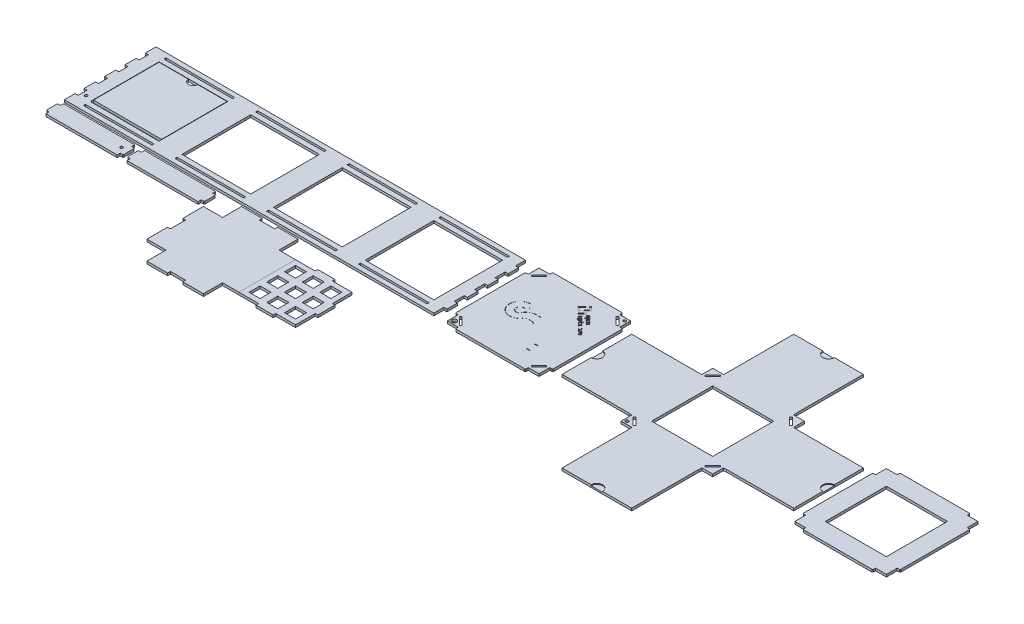
SolidWorks part; units mm, degrees
ref_plane "Front" through (0, 0, 0) normal (0, 0, 1) x (1, 0, 0)
ref_plane "Top" through (0, 0, 0) normal (0, 1, 0) x (1, 0, 0)
ref_plane "Right" through (0, 0, 0) normal (1, 0, 0) x (0, 0, -1)
sketch "Sketch1" plane through (0, 0, 0) normal (0, 1, 0) x (1, 0, 0)
  line L0 (0, 0) -> (228.6, 0) construction
  line L2 (-76.2, 76.2) -> (-76.2, -76.2) construction
  line L4 (76.2, 76.2) -> (76.2, -76.2) construction
  line L5 (-76.2, 76.2) -> (76.2, -76.2) construction
  line L6 (-76.2, -76.2) -> (76.2, 76.2) construction
  line L11 (76.2, 76.2) -> (228.6, 76.2)
  line L12 (76.2, 76.2) -> (76.2, -76.2) construction
  line L13 (76.2, -76.2) -> (228.6, -76.2)
  line L14 (228.6, 76.2) -> (228.6, -76.2) construction
  line L19 (-76.2, -76.2) -> (-228.6, -76.2)
  line L20 (-76.2, -76.2) -> (-76.2, 76.2) construction
  line L21 (-76.2, 76.2) -> (-228.6, 76.2)
  line L28 (76.2, -76.2) -> (-76.2, -76.2)
  line L34 (76.2, 76.2) -> (-76.2, 76.2)
  line L35 (-228.6, 76.2) -> (-228.6, -76.2) construction
  line L43 (-228.6, 76.2) -> (-381, 76.2)
  line L44 (-381, 76.2) -> (-381, -76.2) construction
  line L45 (-381, -76.2) -> (-228.6, -76.2)
  line L46 (228.6, 76.2) -> (228.6, 59.6392)
  line L47 (228.6, 59.6392) -> (233.68, 59.6392)
  line L48 (233.68, 59.6392) -> (233.68, 42.2402)
  line L49 (233.68, 42.2402) -> (228.6, 42.2402)
  line L50 (228.6, 42.2402) -> (228.6, 25.6794)
  line L51 (228.6, 25.6794) -> (233.68, 25.6794)
  line L63 (233.68, 25.6794) -> (233.68, 8.2804)
  line L64 (233.68, 8.2804) -> (228.6, 8.2804)
  line L65 (228.6, 8.2804) -> (228.6, -8.2804)
  line L66 (228.6, -8.2804) -> (233.68, -8.2804)
  line L67 (233.68, -8.2804) -> (233.68, -25.6794)
  line L68 (233.68, -25.6794) -> (228.6, -25.6794)
  line L69 (228.6, -25.6794) -> (228.6, -42.2402)
  line L70 (228.6, -42.2402) -> (233.68, -42.2402)
  line L71 (233.68, -42.2402) -> (233.68, -59.6392)
  line L72 (233.68, -59.6392) -> (228.6, -59.6392)
  line L73 (228.6, -59.6392) -> (228.6, -76.2)
  line L74 (-381, 76.2) -> (-386.08, 76.2)
  line L76 (-386.08, 58.5597) -> (-381, 58.5597)
  line L78 (-381, 43.3197) -> (-386.08, 43.3197)
  line L80 (-386.08, 24.5999) -> (-381, 24.5999)
  line L82 (-381, 9.3599) -> (-386.08, 9.3599)
  line L84 (-386.08, -9.3599) -> (-381, -9.3599)
  line L86 (-381, -24.5999) -> (-386.08, -24.5999)
  line L88 (-386.08, -43.3197) -> (-381, -43.3197)
  line L90 (-381, -58.5597) -> (-386.08, -58.5597)
  line L92 (-386.08, -76.2) -> (-381, -76.2)
  line L93 (233.68, 16.9799) -> (-381, 16.9799) construction
  line L94 (-381, 50.9397) -> (233.68, 50.9397) construction
  line L95 (-386.08, 76.2) -> (-386.08, 58.5597)
  line L96 (-386.08, 43.3197) -> (-386.08, 24.5999)
  line L97 (-381, 58.5597) -> (-381, 43.3197)
  line L98 (-381, 24.5999) -> (-381, 9.3599)
  line L99 (-381, -9.3599) -> (-381, -24.5999)
  line L100 (-381, -43.3197) -> (-381, -58.5597)
  line L101 (-381, -50.9397) -> (233.68, -50.9397) construction
  line L102 (-381, -16.9799) -> (233.68, -16.9799) construction
  line L103 (-386.08, 9.3599) -> (-386.08, -9.3599)
  line L104 (-386.08, -24.5999) -> (-386.08, -43.3197)
  line L105 (-386.08, -58.5597) -> (-386.08, -76.2)
  point P0 (0, 0)
  dimension "D2" = 152.4
  dimension "D1" = 152.4
  dimension "D3" = 5.08
  dimension "D5" = 15.24
  dimension "D4" = 17.399
extrude "Boss-Extrude1" add sketch "Sketch1" along normal blind 4.064
sketch "Sketch4" plane through (0, 4.064, 0) normal (0, 1, 0) x (1, 0, 0)
  line L0 (-228.6, 76.2) -> (-228.6, -76.2) construction
  line L1 (-228.6, 76.2) -> (-228.6, -76.2)
  line L2 (-76.2, 76.2) -> (-76.2, -76.2) construction
  line L3 (-76.2, 76.2) -> (-76.2, -76.2)
  line L4 (76.2, 76.2) -> (76.2, -76.2) construction
  line L5 (76.2, 76.2) -> (76.2, -76.2)
sketch "Sketch5" plane through (0, 4.064, 0) normal (0, 1, 0) x (1, 0, 0)
  line L0 (-381, -9.3599) -> (-381, 9.3599) construction
  line L1 (-228.6, 0) -> (-381, 0) construction
  line L2 (-228.6, 76.2) -> (-228.6, -76.2) construction
  line L3 (-228.6, 0) -> (-76.2, 0) construction
  line L4 (-76.2, 76.2) -> (-76.2, -76.2) construction
  line L5 (-76.2, 0) -> (76.2, 0) construction
  line L6 (76.2, 76.2) -> (76.2, -76.2) construction
  line L7 (76.2, 0) -> (228.6, 0) construction
  line L8 (228.6, -8.2804) -> (228.6, 8.2804) construction
  line L9 (-304.8, 0) -> (-304.8, -76.2) construction
  line L10 (-386.08, -76.2) -> (228.6, -76.2) construction
  line L11 (-152.4, 0) -> (-152.4, -76.2) construction
  line L12 (0, 0) -> (0, -76.2) construction
  line L13 (152.4, 0) -> (152.4, -76.2) construction
  line L14 (-247.65, -68.58) -> (-247.65, -76.2) construction
  line L15 (-361.95, -65.278) -> (-247.65, -65.278)
  line L16 (-361.95, -65.278) -> (-361.95, -68.58)
  line L17 (-361.95, -68.58) -> (-247.65, -68.58)
  line L18 (-247.65, -65.278) -> (-247.65, -68.58)
  line L19 (-361.95, -65.278) -> (-247.65, -68.58) construction
  line L20 (-361.95, -68.58) -> (-247.65, -65.278) construction
  line L21 (-209.55, -65.278) -> (-95.25, -65.278)
  line L22 (-209.55, -65.278) -> (-209.55, -68.58)
  line L23 (-209.55, -68.58) -> (-95.25, -68.58)
  line L24 (-95.25, -65.278) -> (-95.25, -68.58)
  line L25 (-209.55, -65.278) -> (-95.25, -68.58) construction
  line L26 (-209.55, -68.58) -> (-95.25, -65.278) construction
  line L27 (-57.15, -68.58) -> (57.15, -68.58)
  line L28 (-57.15, -68.58) -> (-57.15, -65.278)
  line L29 (-57.15, -65.278) -> (57.15, -65.278)
  line L30 (57.15, -68.58) -> (57.15, -65.278)
  line L31 (-57.15, -68.58) -> (57.15, -65.278) construction
  line L32 (-57.15, -65.278) -> (57.15, -68.58) construction
  line L33 (95.25, -68.58) -> (209.55, -68.58)
  line L34 (95.25, -68.58) -> (95.25, -65.278)
  line L35 (95.25, -65.278) -> (209.55, -65.278)
  line L36 (209.55, -68.58) -> (209.55, -65.278)
  line L37 (95.25, -68.58) -> (209.55, -65.278) construction
  line L38 (95.25, -65.278) -> (209.55, -68.58) construction
  line L39 (95.25, 65.278) -> (209.55, 68.58) construction
  line L40 (95.25, 68.58) -> (209.55, 65.278) construction
  line L41 (-57.15, 65.278) -> (57.15, 68.58) construction
  line L42 (-57.15, 68.58) -> (57.15, 65.278) construction
  line L43 (-209.55, 68.58) -> (-95.25, 65.278) construction
  line L44 (-209.55, 65.278) -> (-95.25, 68.58) construction
  line L45 (-361.95, 68.58) -> (-247.65, 65.278) construction
  line L46 (-361.95, 65.278) -> (-247.65, 68.58) construction
  line L47 (-247.65, 68.58) -> (-247.65, 76.2) construction
  line L48 (209.55, 68.58) -> (209.55, 65.278)
  line L49 (95.25, 65.278) -> (209.55, 65.278)
  line L50 (95.25, 68.58) -> (95.25, 65.278)
  line L51 (95.25, 68.58) -> (209.55, 68.58)
  line L52 (57.15, 68.58) -> (57.15, 65.278)
  line L53 (-57.15, 65.278) -> (57.15, 65.278)
  line L54 (-57.15, 68.58) -> (-57.15, 65.278)
  line L55 (-57.15, 68.58) -> (57.15, 68.58)
  line L56 (-95.25, 65.278) -> (-95.25, 68.58)
  line L57 (-209.55, 68.58) -> (-95.25, 68.58)
  line L58 (-209.55, 65.278) -> (-209.55, 68.58)
  line L59 (-209.55, 65.278) -> (-95.25, 65.278)
  line L60 (-247.65, 65.278) -> (-247.65, 68.58)
  line L61 (-361.95, 68.58) -> (-247.65, 68.58)
  line L62 (-361.95, 65.278) -> (-361.95, 68.58)
  line L63 (-361.95, 65.278) -> (-247.65, 65.278)
  line L64 (228.6, 76.2) -> (-386.08, 76.2) construction
  line L65 (-361.95, 57.15) -> (-247.65, 57.15)
  line L66 (-361.95, 57.15) -> (-361.95, -57.15)
  line L67 (-361.95, -57.15) -> (-247.65, -57.15)
  line L68 (-247.65, 57.15) -> (-247.65, -57.15)
  line L69 (-361.95, 57.15) -> (-247.65, -57.15) construction
  line L70 (-361.95, -57.15) -> (-247.65, 57.15) construction
  line L71 (-209.55, 57.15) -> (-95.25, 57.15)
  line L72 (-209.55, 57.15) -> (-209.55, -57.15)
  line L73 (-209.55, -57.15) -> (-95.25, -57.15)
  line L74 (-95.25, 57.15) -> (-95.25, -57.15)
  line L75 (-209.55, 57.15) -> (-95.25, -57.15) construction
  line L76 (-209.55, -57.15) -> (-95.25, 57.15) construction
  line L77 (-57.15, 57.15) -> (57.15, 57.15)
  line L78 (-57.15, 57.15) -> (-57.15, -57.15)
  line L79 (-57.15, -57.15) -> (57.15, -57.15)
  line L80 (57.15, 57.15) -> (57.15, -57.15)
  line L81 (-57.15, 57.15) -> (57.15, -57.15) construction
  line L82 (-57.15, -57.15) -> (57.15, 57.15) construction
  line L83 (95.25, 57.15) -> (209.55, 57.15)
  line L84 (95.25, 57.15) -> (95.25, -57.15)
  line L85 (95.25, -57.15) -> (209.55, -57.15)
  line L86 (209.55, 57.15) -> (209.55, -57.15)
  line L87 (95.25, 57.15) -> (209.55, -57.15) construction
  line L88 (95.25, -57.15) -> (209.55, 57.15) construction
  circle A0 centre (-373.95, -52.15) radius 2.2225
  point P27 (-304.8, -66.929)
  point P32 (-152.4, -66.929)
  point P37 (0, -66.929)
  point P42 (152.4, -66.929)
  point P66 (152.4, 66.929)
  point P67 (0, 66.929)
  point P68 (-152.4, 66.929)
  point P69 (-304.8, 66.929)
  dimension "D5" = 4.445
  dimension "D7" = 5
  dimension "D1" = 7.62
  dimension "D2" = 3.302
  dimension "D3" = 114.3
  dimension "D4" = 19.05
  dimension "D6" = 12
  dimension "D8" = 19.05
extrude "Cut-Extrude2" cut sketch "Sketch5" against normal through all
sketch "Sketch6" plane through (0, 0, 0) normal (0, 1, 0) x (1, 0, 0)
  line L0 (0, 0) -> (327.3425, 0) construction
  line L1 (327.3425, 0) -> (327.3425, 78.5813) construction
  line L2 (251.1425, 76.2) -> (403.5425, 76.2) construction
  line L3 (251.1425, 76.2) -> (251.1425, -76.2) construction
  line L4 (251.1425, -76.2) -> (403.5425, -76.2) construction
  line L5 (403.5425, 76.2) -> (403.5425, -76.2) construction
  line L6 (251.1425, 76.2) -> (403.5425, -76.2) construction
  line L7 (251.1425, -76.2) -> (403.5425, 76.2) construction
  line L8 (327.3425, 0) -> (405.9238, 0) construction
  line L9 (327.3425, 0) -> (327.3425, -78.5813) construction
  line L10 (251.1425, 58.2612) -> (251.1425, 76.2)
  line L11 (269.0813, 80.9625) -> (385.6038, 80.9625)
  line L12 (269.0813, 80.9625) -> (269.0813, 76.2)
  line L13 (269.0813, 76.2) -> (385.6038, 76.2) construction
  line L14 (385.6038, 80.9625) -> (385.6038, 76.2)
  line L15 (269.0813, 80.9625) -> (385.6038, 76.2) construction
  line L16 (269.0813, 76.2) -> (385.6038, 80.9625) construction
  line L17 (408.305, -58.2612) -> (403.5425, -58.2612)
  line L18 (408.305, -58.2612) -> (408.305, 58.2612)
  line L19 (408.305, 58.2612) -> (403.5425, 58.2612)
  line L20 (403.5425, -58.2612) -> (403.5425, 58.2612) construction
  line L21 (408.305, -58.2612) -> (403.5425, 58.2612) construction
  line L22 (408.305, 58.2612) -> (403.5425, -58.2612) construction
  line L23 (269.0813, -80.9625) -> (385.6037, -80.9625)
  line L24 (269.0813, -80.9625) -> (269.0813, -76.2)
  line L25 (269.0813, -76.2) -> (385.6037, -76.2) construction
  line L26 (385.6037, -80.9625) -> (385.6037, -76.2)
  line L27 (269.0813, -80.9625) -> (385.6037, -76.2) construction
  line L28 (269.0813, -76.2) -> (385.6037, -80.9625) construction
  line L29 (246.38, 58.2612) -> (251.1425, 58.2612)
  line L30 (246.38, 58.2612) -> (246.38, -58.2612)
  line L31 (246.38, -58.2612) -> (251.1425, -58.2612)
  line L32 (251.1425, 58.2612) -> (251.1425, -58.2612) construction
  line L33 (246.38, 58.2612) -> (251.1425, -58.2612) construction
  line L34 (246.38, -58.2612) -> (251.1425, 58.2612) construction
  line L35 (251.1425, 76.2) -> (269.0813, 76.2)
  line L36 (385.6038, 76.2) -> (403.5425, 76.2)
  line L37 (403.5425, 76.2) -> (403.5425, 58.2612)
  line L38 (403.5425, -58.2612) -> (403.5425, -76.2)
  line L39 (403.5425, -76.2) -> (385.6037, -76.2)
  line L40 (269.0813, -76.2) -> (251.1425, -76.2)
  line L41 (251.1425, -76.2) -> (251.1425, -58.2612)
  line L42 (535.305, 58.2612) -> (535.305, -58.2612)
  line L43 (535.305, 58.2612) -> (540.0675, 58.2612)
  line L44 (540.0675, 58.2612) -> (540.0675, 76.2)
  line L45 (540.0675, 76.2) -> (558.0063, 76.2)
  line L46 (558.0063, 80.9625) -> (558.0063, 76.2)
  line L47 (558.0063, 80.9625) -> (674.5288, 80.9625)
  line L48 (674.5288, 80.9625) -> (674.5288, 76.2)
  line L49 (674.5288, 76.2) -> (692.4675, 76.2)
  line L50 (692.4675, 76.2) -> (692.4675, 58.2612)
  line L51 (697.23, 58.2612) -> (692.4675, 58.2612)
  line L52 (697.23, -58.2612) -> (697.23, 58.2612)
  line L53 (697.23, -58.2612) -> (692.4675, -58.2612)
  line L54 (692.4675, -58.2612) -> (692.4675, -76.2)
  line L55 (692.4675, -76.2) -> (674.5287, -76.2)
  line L56 (674.5287, -80.9625) -> (674.5287, -76.2)
  line L57 (558.0063, -80.9625) -> (674.5287, -80.9625)
  line L58 (558.0063, -80.9625) -> (558.0063, -76.2)
  line L59 (558.0063, -76.2) -> (540.0675, -76.2)
  line L60 (540.0675, -76.2) -> (540.0675, -58.2612)
  line L61 (535.305, -58.2612) -> (540.0675, -58.2612)
  line L62 (540.0675, 76.2) -> (692.4675, -76.2) construction
  line L63 (824.23, 58.2612) -> (824.23, -58.2612)
  line L64 (824.23, 58.2612) -> (828.9925, 58.2612)
  line L65 (828.9925, 58.2612) -> (828.9925, 76.2)
  line L66 (828.9925, 76.2) -> (846.9313, 76.2)
  line L67 (846.9313, 80.9625) -> (846.9313, 76.2)
  line L68 (846.9313, 80.9625) -> (963.4538, 80.9625)
  line L69 (963.4538, 80.9625) -> (963.4538, 76.2)
  line L70 (963.4538, 76.2) -> (981.3925, 76.2)
  line L71 (981.3925, 76.2) -> (981.3925, 58.2612)
  line L72 (986.155, 58.2612) -> (981.3925, 58.2612)
  line L73 (986.155, -58.2612) -> (986.155, 58.2612)
  line L74 (986.155, -58.2612) -> (981.3925, -58.2612)
  line L75 (981.3925, -58.2612) -> (981.3925, -76.2)
  line L76 (981.3925, -76.2) -> (963.4537, -76.2)
  line L77 (963.4537, -80.9625) -> (963.4537, -76.2)
  line L78 (846.9313, -80.9625) -> (963.4537, -80.9625)
  line L79 (846.9313, -80.9625) -> (846.9313, -76.2)
  line L80 (846.9313, -76.2) -> (828.9925, -76.2)
  line L81 (828.9925, -76.2) -> (828.9925, -58.2612)
  line L82 (824.23, -58.2612) -> (828.9925, -58.2612)
  line L83 (828.9925, 76.2) -> (981.3925, -76.2) construction
  line L84 (565.4675, 50.8) -> (667.0675, 50.8)
  line L85 (565.4675, 50.8) -> (565.4675, -50.8)
  line L86 (565.4675, -50.8) -> (667.0675, -50.8)
  line L87 (667.0675, 50.8) -> (667.0675, -50.8)
  line L88 (565.4675, 50.8) -> (667.0675, -50.8) construction
  line L89 (565.4675, -50.8) -> (667.0675, 50.8) construction
  line L90 (233.68, -25.6794) -> (233.68, -8.2804) construction
  line L91 (955.9925, 50.8) -> (854.3925, 50.8)
  line L92 (955.9925, 50.8) -> (955.9925, -50.8)
  line L93 (955.9925, -50.8) -> (854.3925, -50.8)
  line L94 (854.3925, 50.8) -> (854.3925, -50.8)
  line L95 (955.9925, 50.8) -> (854.3925, -50.8) construction
  line L96 (955.9925, -50.8) -> (854.3925, 50.8) construction
  line L97 (-76.2, -57.15) -> (76.2, -57.15) construction
  line L98 (-76.2, 76.2) -> (-76.2, -76.2) construction
  line L99 (76.2, 76.2) -> (76.2, -76.2) construction
  line L100 (76.2, -57.15) -> (228.6, -57.15) construction
  line L101 (228.6, -76.2) -> (228.6, -59.6392) construction
  line L102 (-57.15, -57.15) -> (57.15, -57.15) construction
  line L103 (95.25, 57.15) -> (209.55, 57.15) construction
  point P22 (248.7613, 0)
  point P67 (616.2675, 0)
  point P72 (905.1925, 0)
  dimension "D3" = 4.7625
  dimension "D8" = 101.6
  dimension "D5" = 12.7
  dimension "D1" = 114.3
  dimension "D2" = 116.5225
  dimension "D4" = 127
  dimension "D6" = 3
extrude "Boss-Extrude2" add sketch "Sketch6" along normal blind 4.064 separate body
sketch "Sketch7" plane through (0, 0, 0) normal (0, 1, 0) x (1, 0, 0)
  line L0 (-361.95, 65.278) -> (-361.95, -53.086) construction
  line L1 (-381.08, -82.55) -> (-262.716, -82.55)
  line L2 (-381.08, -82.55) -> (-381.08, -87.63)
  line L3 (-381.08, -111.76) -> (-262.716, -111.76)
  line L4 (-262.716, -82.55) -> (-262.716, -87.63)
  line L5 (-381.08, -82.55) -> (-262.716, -111.76) construction
  line L6 (-381.08, -111.76) -> (-262.716, -82.55) construction
  line L7 (-361.95, 57.15) -> (-361.95, -57.15) construction
  line L8 (-361.95, -53.086) -> (-361.95, -57.15) construction
  line L9 (251.1425, -58.2612) -> (251.1425, -76.2) construction
  line L10 (251.1425, -76.2) -> (269.0813, -76.2) construction
  line L12 (-381.08, -87.63) -> (-386.08, -87.63)
  line L13 (257.0586, -57.7116) -> (269.6309, -70.2839) construction
  line L14 (257.0586, -57.7116) -> (254.7237, -60.0464) construction
  line L15 (254.7237, -60.0464) -> (267.2961, -72.6188) construction
  line L16 (269.6309, -70.2839) -> (267.2961, -72.6188) construction
  line L17 (257.0586, -57.7116) -> (267.2961, -72.6188) construction
  line L18 (254.7237, -60.0464) -> (269.6309, -70.2839) construction
  line L19 (-386.08, -87.63) -> (-386.08, -106.68)
  line L20 (-386.08, -106.68) -> (-381.08, -106.68)
  line L22 (262.1773, -65.1652) -> (260.1119, -67.2306) construction
  line L23 (-381.08, -106.68) -> (-381.08, -111.76)
  line L24 (-262.716, -87.63) -> (-257.716, -87.63)
  line L25 (-257.716, -87.63) -> (-257.716, -106.68)
  line L26 (-257.716, -106.68) -> (-262.716, -106.68)
  line L27 (-262.716, -106.68) -> (-262.716, -111.76)
  line L28 (-386.08, -76.2) -> (228.6, -76.2) construction
  line L29 (-386.08, -58.5597) -> (-386.08, -76.2) construction
  line L30 (-246.366, -82.55) -> (-128.002, -82.55)
  line L31 (-246.366, -82.55) -> (-246.366, -87.63)
  line L32 (-246.366, -111.76) -> (-128.002, -111.76)
  line L33 (-128.002, -82.55) -> (-128.002, -87.63)
  line L34 (-246.366, -87.63) -> (-251.366, -87.63)
  line L35 (-251.366, -87.63) -> (-251.366, -106.68)
  line L36 (-251.366, -106.68) -> (-246.366, -106.68)
  line L37 (-246.366, -106.68) -> (-246.366, -111.76)
  line L38 (-128.002, -87.63) -> (-123.002, -87.63)
  line L39 (-123.002, -87.63) -> (-123.002, -106.68)
  line L40 (-123.002, -106.68) -> (-128.002, -106.68)
  line L41 (-128.002, -106.68) -> (-128.002, -111.76)
  line L42 (-246.366, -82.55) -> (-128.002, -111.76) construction
  line L43 (-246.366, -111.76) -> (-128.002, -82.55) construction
  line L44 (-361.95, 65.278) -> (-386.08, 65.278) construction
  line L45 (-386.08, 76.2) -> (-386.08, 58.5597) construction
  line L46 (251.1425, -58.2612) -> (269.0813, -76.2) construction
  point P0 (-321.898, -97.155)
  point P14 (262.1773, -65.1652)
  point P38 (-187.184, -97.155)
  dimension "D1" = 29.21
  dimension "D2" = 4.064
  dimension "D3" = 3.302
  dimension "D4" = 19.05
  dimension "D5" = 17.78
  dimension "D6" = 5
  dimension "D7" = 6.35
  dimension "D9" = 6.35
  dimension "D10" = 1.27
  dimension "D8" = 2
extrude "PILLAR POSITION" add sketch "Sketch7" along normal blind 4.064 separate body
sketch "Sketch8" plane through (0, 4.064, 0) normal (0, 1, 0) x (1, 0, 0)
  line L0 (254.7237, -60.0464) -> (267.2961, -72.6188) construction
  line L1 (269.6309, -70.2839) -> (267.2961, -72.6188) construction
  line L2 (257.0586, -57.7116) -> (269.6309, -70.2839) construction
  line L3 (257.0586, -57.7116) -> (254.7237, -60.0464) construction
  line L4 (254.7237, -60.0464) -> (267.2961, -72.6188)
  line L5 (269.6309, -70.2839) -> (267.2961, -72.6188)
  line L6 (257.0586, -57.7116) -> (269.6309, -70.2839)
  line L7 (257.0586, -57.7116) -> (254.7237, -60.0464)
  line L8 (251.1425, 76.2) -> (403.5425, -76.2) construction
  line L9 (269.6309, 70.2839) -> (257.0586, 57.7116)
  line L10 (269.6309, 70.2839) -> (267.2961, 72.6188)
  line L11 (267.2961, 72.6188) -> (254.7237, 60.0464)
  line L12 (257.0586, 57.7116) -> (254.7237, 60.0464)
  line L13 (397.6264, 57.7116) -> (385.0541, 70.2839)
  line L14 (397.6264, 57.7116) -> (399.9613, 60.0464)
  line L15 (399.9613, 60.0464) -> (387.3889, 72.6188)
  line L16 (385.0541, 70.2839) -> (387.3889, 72.6188)
  line L17 (385.0541, -70.2839) -> (397.6264, -57.7116)
  line L18 (385.0541, -70.2839) -> (387.3889, -72.6188)
  line L19 (387.3889, -72.6188) -> (399.9613, -60.0464)
  line L20 (397.6264, -57.7116) -> (399.9613, -60.0464)
  line L21 (540.0675, -58.2612) -> (558.0063, -76.2) construction
  line L22 (543.6487, -60.0464) -> (545.9836, -57.7116)
  line L23 (545.9836, -57.7116) -> (558.5559, -70.2839)
  line L24 (558.5559, -70.2839) -> (556.2211, -72.6188)
  line L25 (549.0369, -67.2306) -> (552.2698, -63.9977) construction
  line L26 (543.6487, -60.0464) -> (556.2211, -72.6188)
  line L27 (540.0675, 76.2) -> (692.4675, -76.2) construction
  line L28 (545.9836, 57.7116) -> (543.6487, 60.0464)
  line L29 (556.2211, 72.6188) -> (543.6487, 60.0464)
  line L30 (556.2211, 72.6188) -> (558.5559, 70.2839)
  line L31 (558.5559, 70.2839) -> (545.9836, 57.7116)
  line L32 (673.9791, 70.2839) -> (676.3139, 72.6188)
  line L33 (688.8863, 60.0464) -> (676.3139, 72.6188)
  line L34 (688.8863, 60.0464) -> (686.5514, 57.7116)
  line L35 (686.5514, 57.7116) -> (673.9791, 70.2839)
  line L36 (686.5514, -57.7116) -> (688.8863, -60.0464)
  line L37 (676.3139, -72.6188) -> (688.8863, -60.0464)
  line L38 (676.3139, -72.6188) -> (673.9791, -70.2839)
  line L39 (673.9791, -70.2839) -> (686.5514, -57.7116)
  line L40 (251.1425, -58.2612) -> (269.0813, -76.2) construction
  line L41 (261.0099, -66.3326) -> (260.1119, -67.2306) construction
  line L42 (556.2211, -72.6188) -> (555.3231, -73.5168) construction
  circle A0 centre (327.3425, 0) radius 20.7898 construction
  circle A1 centre (327.3425, 0) radius 20.7898 construction
  circle A2 centre (327.3425, 0) radius 20.7898 construction
  circle A3 centre (327.3425, 0) radius 20.7898 construction
  circle A4 centre (616.2675, 0) radius 71.842 construction
  point P28 (327.3425, 0)
  point P58 (616.2675, 0)
  dimension "D1" = 4
  dimension "D2" = 4
extrude "Cut-Extrude3" cut sketch "Sketch8" against normal through all
sketch "Sketch10" plane through (0, 4.064, 0) normal (0, 1, 0) x (1, 0, 0)
  line L0 (-247.65, 57.15) -> (-361.95, 57.15) construction
  line L1 (-95.25, 57.15) -> (-209.55, 57.15) construction
  line L2 (57.15, 57.15) -> (-57.15, 57.15) construction
  line L3 (209.55, 57.15) -> (95.25, 57.15) construction
  line L4 (-296.8, 57.15) -> (-312.8, 57.15)
  line L5 (-144.4, 57.15) -> (-160.4, 57.15)
  line L6 (8, 57.15) -> (-8, 57.15)
  line L7 (160.4, 57.15) -> (144.4, 57.15)
  line L8 (-361.95, -53.086) -> (-247.65, -53.086)
  line L9 (-304.8, -53.086) -> (-304.8, -57.15) construction
  line L14 (-361.95, 57.15) -> (-361.95, -57.15) construction
  line L15 (-247.65, -57.15) -> (-247.65, 57.15) construction
  line L16 (-361.95, -57.15) -> (-247.65, -57.15) construction
  line L17 (-209.55, -53.086) -> (-95.25, -53.086)
  line L18 (-209.55, 57.15) -> (-209.55, -57.15) construction
  line L19 (-95.25, -57.15) -> (-95.25, 57.15) construction
  line L20 (-57.15, -53.086) -> (57.15, -53.086)
  line L21 (-57.15, 57.15) -> (-57.15, -57.15) construction
  line L22 (57.15, -57.15) -> (57.15, 57.15) construction
  line L23 (95.25, -53.086) -> (209.55, -53.086)
  line L24 (95.25, 57.15) -> (95.25, -57.15) construction
  line L25 (209.55, -57.15) -> (209.55, 57.15) construction
  line L27 (-361.95, 57.15) -> (-361.95, -53.086) construction
  arc A0 (-312.8, 57.15) -> (-296.8, 57.15) centre (-304.8, 57.15) ccw
  arc A1 (-160.4, 57.15) -> (-144.4, 57.15) centre (-152.4, 57.15) ccw
  arc A2 (-8, 57.15) -> (8, 57.15) centre (0, 57.15) ccw
  arc A3 (144.4, 57.15) -> (160.4, 57.15) centre (152.4, 57.15) ccw
  point P49 (0, 0)
  dimension "D1" = 16
  dimension "D2" = 4.064
sketch "Sketch18" plane through (0, 4.064, 0) normal (0, 1, 0) x (1, 0, 0)
  line L0 (-361.95, 57.15) -> (-247.65, -53.086) construction
  line L6 (-247.65, 57.15) -> (-361.95, 57.15) construction
  line L7 (-361.3901, 56.61) -> (-312.7818, 56.61)
  line L9 (-361.3901, 56.61) -> (-361.3901, -52.546)
  line L10 (-361.3901, -52.546) -> (-248.2099, -52.546)
  line L11 (-248.2099, 56.61) -> (-248.2099, -52.546)
  line L12 (-361.3901, 56.61) -> (-248.2099, -52.546) construction
  line L13 (-361.3901, -52.546) -> (-248.2099, 56.61) construction
  line L14 (-296.8182, 56.61) -> (-248.2099, 56.61)
  arc A2 (-312.8, 57.15) -> (-296.8, 57.15) centre (-304.8, 57.15) ccw construction
  arc A3 (-312.7818, 56.61) -> (-296.8182, 56.61) centre (-304.8, 57.15) ccw
  point P4 (-304.8, 2.032)
  dimension "D1" = 0.54
extrude "Boss-Extrude8" add sketch "Sketch18" against normal blind 4.064 separate body
sketch "Sketch11" plane through (0, 0, 0) normal (0, 1, 0) x (1, 0, 0)
  line L0 (-209.55, -57.15) -> (-209.55, -65.278) construction
  line L5 (-84.902, -114.3) -> (9.078, -114.3) construction
  line L6 (-84.902, -114.3) -> (-84.902, -208.28) construction
  line L7 (-84.902, -208.28) -> (9.078, -208.28) construction
  line L8 (9.078, -114.3) -> (9.078, -208.28) construction
  line L9 (-84.902, -114.3) -> (9.078, -208.28) construction
  line L10 (-84.902, -208.28) -> (9.078, -114.3) construction
  line L11 (-84.902, -114.3) -> (-116.652, -114.3)
  line L12 (-116.652, -114.3) -> (-116.652, -208.28)
  line L13 (-116.652, -208.28) -> (-84.902, -208.28)
  line L14 (-84.902, -114.3) -> (-84.902, -82.55)
  line L15 (-84.902, -82.55) -> (9.078, -82.55)
  line L16 (9.078, -82.55) -> (9.078, -114.3)
  line L17 (9.078, -114.3) -> (36.51, -114.3)
  line L18 (36.51, -114.3) -> (36.51, -208.28)
  line L19 (36.51, -208.28) -> (9.078, -208.28)
  line L20 (9.078, -208.28) -> (9.078, -240.03)
  line L21 (9.078, -240.03) -> (-84.902, -240.03)
  line L22 (-84.902, -240.03) -> (-84.902, -208.28)
  line L23 (-386.08, -76.2) -> (228.6, -76.2) construction
  line L24 (-123.002, -106.68) -> (-123.002, -87.63) construction
  line L25 (-209.55, -57.15) -> (-95.25, -57.15) construction
  line L26 (565.4675, -50.8) -> (667.0675, -50.8) construction
  line L27 (209.55, -53.086) -> (209.55, -76.2) construction
  line L28 (-88.966, -237.49) -> (13.142, -237.49) construction
  line L29 (-37.912, -161.29) -> (-37.912, -237.49) construction
  line L30 (-88.966, -237.49) -> (-88.966, -240.03) construction
  line L31 (-88.966, -240.03) -> (-84.902, -240.03) construction
  line L32 (9.078, -240.03) -> (13.142, -240.03) construction
  line L33 (13.142, -240.03) -> (13.142, -237.49) construction
  point P0 (-37.912, -161.29)
  point P33 (-37.912, -237.49)
  dimension "D1" = 4.064
  dimension "D2" = 101.6
  dimension "D3" = 102.108
  dimension "D4" = 6.35
  dimension "D5" = 6.35
  dimension "D6" = 2.54
  dimension "D7" = 31.75
  dimension "D8" = 27.432
extrude "Boss-Extrude5" add sketch "Sketch11" along normal blind 4.064 separate body
sketch "Sketch12" plane through (0, 4.064, 0) normal (0, 1, 0) x (1, 0, 0)
  line L0 (-84.902, -114.3) -> (9.078, -114.3)
  line L1 (9.078, -114.3) -> (9.078, -208.28)
  line L2 (9.078, -208.28) -> (-84.902, -208.28)
  line L3 (-84.902, -114.3) -> (-84.902, -208.28)
sketch "Sketch13" plane through (0, 0, 0) normal (0, 1, 0) x (1, 0, 0)
  line L16 (-223.9443, 14.6616) -> (-211.1797, 14.6616)
  line L17 (-211.1797, 14.6616) -> (-211.1797, 5.1786)
  line L18 (-211.1797, 5.1786) -> (-201.7193, 5.1786)
  line L19 (350.3041, 64.4565) -> (356.7512, 58.0094)
  line L20 (356.7512, 58.0094) -> (351.9616, 53.2197)
  line L21 (351.9616, 53.2197) -> (356.7398, 48.4415)
  line L22 (356.7398, 48.4415) -> (350.2812, 41.983)
  line L24 (348.6694, 43.5948) -> (353.4934, 48.4187)
  line L25 (353.4934, 48.4187) -> (348.7266, 53.1854)
  line L26 (348.7266, 53.1854) -> (353.5391, 57.9979)
  line L27 (353.5391, 57.9979) -> (348.6923, 62.8447)
  line L28 (348.6923, 62.8447) -> (350.3041, 64.4565)
  line L29 (345.5145, 59.6669) -> (347.1377, 58.0437)
  line L30 (347.1377, 58.0437) -> (342.3023, 53.2083)
  line L31 (342.3023, 53.2083) -> (347.1262, 48.3844)
  line L32 (347.1262, 48.3844) -> (345.503, 46.7612)
  line L33 (345.503, 46.7612) -> (339.0559, 53.2083)
  line L34 (339.0559, 53.2083) -> (345.5145, 59.6669)
  line L36 (350.7409, 41.9187) -> (377.6929, 14.9667) construction
  line L37 (358.5912, 47.064) -> (396.3306, 9.3246) construction
  line L38 (348.6694, 43.5948) -> (350.2812, 41.983)
  line L41 (-201.7193, 5.1786) -> (-201.7193, -7.6086)
  line L43 (-204.9105, -7.6086) -> (-204.9105, 1.9422)
  line L44 (-204.9105, 1.9422) -> (-214.3482, 1.9422)
  line L45 (-214.3482, 1.9422) -> (-214.3482, 11.4705)
  line L46 (-214.3482, 11.4705) -> (-223.9443, 11.4705)
  line L47 (-223.9443, 11.4705) -> (-223.9443, 14.6616)
  line L48 (-223.9443, 5.1786) -> (-220.7305, 5.1786)
  line L49 (-220.7305, 5.1786) -> (-220.7305, -4.3949)
  line L50 (-220.7305, -4.3949) -> (-211.1797, -4.3949)
  line L51 (-211.1797, -4.3949) -> (-211.1797, -7.6086)
  line L52 (-211.1797, -7.6086) -> (-223.9443, -7.6086)
  line L53 (-223.9443, -7.6086) -> (-223.9443, 5.1786)
  line L54 (-200.854, -7.608) -> (-149.188, -7.608) construction
  line L55 (-361.95, 57.15) -> (-247.65, -53.086) construction
  line L56 (-204.9105, -7.6086) -> (-201.7193, -7.6086)
  line L57 (-200.854, -7.608) -> (-200.854, 5.1786) construction
  line L58 (-200.854, 5.1786) -> (-201.7193, 5.1786) construction
  line L59 (-200.854, 1.9422) -> (-182.9615, 1.9422) construction
  line L60 (-200.854, -2.3557) -> (-181.4784, -2.3557) construction
  line L61 (-361.95, 57.15) -> (-361.95, -57.15) construction
  line L62 (-273.05, 31.75) -> (-336.55, 31.75) construction
  line L63 (-273.05, 31.75) -> (-273.05, -27.686) construction
  line L64 (-273.05, -27.686) -> (-336.55, -27.686) construction
  line L65 (-336.55, 31.75) -> (-336.55, -27.686) construction
  line L66 (-273.05, 31.75) -> (-336.55, -27.686) construction
  line L67 (-273.05, -27.686) -> (-336.55, 31.75) construction
  line L68 (-247.65, 57.15) -> (-361.95, 57.15) construction
  line L69 (-361.95, -53.086) -> (-247.65, -53.086) construction
  line L70 (-247.65, -57.15) -> (-247.65, 57.15) construction
  text T0 "mit" font "Arial" height in points 18
  text T1 "media" font "Arial" height in points 18
  text T2 "lab" font "Arial" height in points 18
  text T3 "open" font "Arial" height in points 24
  text T4 " agriculture" font "Arial" height in points 24
  point P56 (-194.7375, 4.459)
  dimension "D1" = 25.4
  dimension "D4" = 25.4
  dimension "D5" = 25.4
  dimension "D6" = 25.4
sketch "Sketch14" plane through (0, 4.064, 0) normal (0, 1, 0) x (1, 0, 0)
  line L0 (-257.716, -97.155) -> (-269.9385, -97.155) construction
  line L1 (-257.716, -106.68) -> (-257.716, -87.63) construction
  circle A0 centre (-269.9385, -97.155) radius 2.2225
  circle A1 centre (-373.95, -52.15) radius 2.2225 construction
  dimension "D1" = 10
extrude "Cut-Extrude4" cut sketch "Sketch14" against normal through all
sketch "Sketch15" plane through (0, 4.064, 0) normal (0, 1, 0) x (1, 0, 0)
  line L0 (251.1425, -76.2) -> (261.0099, -66.3326) construction
  line L1 (254.7237, -60.0464) -> (267.2961, -72.6188) construction
  line L2 (256.9227, -76.5158) -> (256.9227, -76.2) construction
  line L3 (251.1425, -76.2) -> (269.0813, -76.2) construction
  line L4 (261.0099, -66.3326) -> (261.2332, -66.1093) construction
  line L5 (251.1425, 76.2) -> (403.5425, -76.2) construction
  line L6 (403.5425, 76.2) -> (393.6751, 66.3326) construction
  line L7 (399.9613, 60.0464) -> (387.3889, 72.6188) construction
  line L8 (549.9349, -66.3326) -> (540.0675, -76.2) construction
  line L9 (543.6487, -60.0464) -> (556.2211, -72.6188) construction
  circle A0 centre (256.9227, -70.4198) radius 3.95
  circle A1 centre (256.9227, -70.4198) radius 6.096 construction
  circle A2 centre (398.6088, 71.2663) radius 2.2225
  circle A3 centre (-269.9385, -97.155) radius 2.2225 construction
  circle A4 centre (545.0012, -71.2663) radius 2.413
  dimension "D1" = 7.9
  dimension "D2" = 12.192
  dimension "D3" = 4.826
extrude "Cut-Extrude5" cut sketch "Sketch15" against normal through all
sketch "Sketch16" plane through (0, 4.064, 0) normal (0, 1, 0) x (1, 0, 0)
  line L0 (565.4675, 50.8) -> (565.4675, -50.8) construction
  line L1 (568.6425, 19.05) -> (481.6251, 19.05) construction
  line L2 (568.6425, 38.1) -> (606.7425, 38.1)
  line L3 (568.6425, 38.1) -> (568.6425, 0)
  line L4 (568.6425, 0) -> (606.7425, 0)
  line L6 (568.6425, 38.1) -> (606.7425, 0) construction
  line L7 (568.6425, 0) -> (606.7425, 38.1) construction
  line L8 (481.6251, 19.05) -> (587.6925, 19.05) construction
  line L9 (606.7425, 38.1) -> (606.7425, 21.4244)
  line L10 (611.1573, 24.6016) -> (611.0727, 24.7481)
  line L11 (587.6925, 38.1) -> (587.6925, 0) construction
  line L12 (600.3925, 24.13) -> (590.9945, 24.13)
  line L13 (600.3925, 13.97) -> (590.9945, 13.97)
  line L14 (587.6925, 24.13) -> (587.6925, 13.97) construction
  line L15 (610.8065, 24.13) -> (587.6925, 24.13) construction
  line L16 (610.8065, 13.97) -> (587.6925, 13.97) construction
  line L17 (603.5958, 23.2628) -> (608.2567, 20.5397)
  line L18 (610.8065, 19.05) -> (610.0837, 19.05) construction
  line L19 (610.8065, 19.05) -> (587.6925, 19.05) construction
  line L20 (626.0626, 19.05) -> (610.0837, 19.05) construction
  line L21 (600.3925, 24.13) -> (600.3925, 13.97) construction
  line L22 (606.7425, -9.6369) -> (606.7425, 0)
  line L23 (667.0675, 50.8) -> (565.4675, 50.8) construction
  line L24 (587.6925, 27.432) -> (587.6925, 27.94) construction
  line L25 (587.6925, 10.668) -> (587.6925, 10.16) construction
  line L26 (587.6925, 27.432) -> (587.6925, 10.668)
  arc A1 (611.1967, 17.4306) -> (614.4843, 22.6039) centre (614.3625, 19.05) ccw
  arc A3 (614.6273, 30.7471) -> (611.0727, 24.7481) centre (614.5368, 26.7481) ccw
  arc A4 (611.1573, 24.6016) -> (614.4843, 22.6039) centre (614.6214, 26.6016) ccw
  arc A5 (603.5958, 23.2628) -> (600.3925, 24.13) centre (600.3925, 17.78) ccw
  arc A6 (605.3071, 11.6411) -> (600.3925, 13.97) centre (600.3925, 7.62) ccw
  arc A7 (611.1967, 17.4306) -> (608.2567, 20.5397) centre (604.4127, 13.9603) ccw
  arc A8 (590.9945, 13.97) -> (587.6925, 10.668) centre (590.9945, 10.668) ccw
  arc A9 (587.6925, 27.432) -> (590.9945, 24.13) centre (590.9945, 27.432) ccw
  arc A10 (605.3071, 11.6411) -> (614.6273, 30.7471) centre (614.3625, 19.05) ccw
  point P4 (587.6925, 19.05)
  point P28 (371.8905, 14.7821)
  dimension "D7" = 4
  dimension "D8" = 6.35
  dimension "D9" = 6.35
  dimension "D10" = 7.62
  dimension "D12" = 7.112
  dimension "D17" = 3.302
  dimension "D1" = 38.1
  dimension "D2" = 38.1
  dimension "D3" = 12.7
  dimension "D4" = 5.08
  dimension "D6" = 30
  dimension "D11" = 26.67
  dimension "D13" = 3.175
  dimension "D14" = 12.7
  dimension "D15" = 3.81
  dimension "D16" = 3.81
  dimension "D5" = 5.08
sketch "Sketch17" plane through (0, 4.064, 0) normal (0, 1, 0) x (1, 0, 0)
  line L1 (327.3425, 80.9625) -> (327.3425, -80.9625) construction
  line L12 (385.6038, 80.9625) -> (269.0813, 80.9625) construction
  line L13 (269.0813, -80.9625) -> (385.6037, -80.9625) construction
  line L30 (327.3425, 10.16) -> (327.3425, -10.16) construction
  line L31 (295.5925, 0) -> (359.0925, 0) construction
  line L32 (305.0305, 2.1893) -> (310.1105, 5.1321)
  line L34 (322.4238, -6.35) -> (314.6425, -6.35)
  line L35 (314.6425, 6.35) -> (322.4238, 6.35)
  arc A9 (310.1105, 5.1321) -> (314.6425, 6.35) centre (314.6425, -2.6913) cw
  arc A10 (301.6187, -2.0019) -> (305.0305, 2.1893) centre (308.8501, -4.4043) cw
  arc A11 (301.6187, -2.0019) -> (295.8598, 6.3444) centre (295.5925, 0) cw
  arc A14 (310.4981, -8.7261) -> (296.3195, 17.2567) centre (295.5925, 0) cw
  arc A15 (310.4981, -8.7261) -> (314.6425, -6.35) centre (314.6425, -11.1524) cw
  arc A16 (322.4238, -6.35) -> (327.3425, -10.16) centre (322.4238, -11.43) cw
  arc A17 (327.3425, 10.16) -> (322.4238, 6.35) centre (322.4238, 11.43) cw
  arc A36 (296.3195, 17.2567) -> (295.8598, 6.3444) centre (296.0896, 11.8005) cw
  point P43 (327.3425, 0)
  point P64 (327.3425, 0)
  dimension "D4" = 17.272
  dimension "D5" = 12.7
  dimension "D6" = 5.08
  dimension "D2" = 31.75
  dimension "D3" = 6.35
  dimension "D8" = 0.4971
  dimension "D9" = 7.62
  dimension "D7" = 20.32
  dimension "D10" = 5.08
  dimension "D11" = 12.7
  dimension "D12" = 30.084
extrude "Cut-Extrude-Thin1" cut sketch "Sketch17" against normal through all thin contours A16 L34 A15 A14 A36 A11 A10 L32 A9 L35 A17 thin type one direction wall 0.25
extrude "Cut-Extrude6" cut sketch "Sketch13" against normal blind 1.27 from surface starting at face at (-304.8, 4.064, -18.9813)
sketch "Sketch19" plane through (0, 4.064, 0) normal (0, 1, 0) x (1, 0, 0)
  line L0 (36.51, -114.3) -> (130.49, -208.28) construction
  line L1 (36.51, -114.3) -> (130.49, -114.3)
  line L2 (36.51, -114.3) -> (36.51, -208.28)
  line L3 (36.51, -208.28) -> (130.49, -208.28)
  line L4 (130.49, -114.3) -> (130.49, -208.28)
  line L6 (54.036, -131.826) -> (112.964, -131.826) construction
  line L7 (54.036, -131.826) -> (54.036, -190.754) construction
  line L8 (54.036, -190.754) -> (112.964, -190.754) construction
  line L9 (112.964, -131.826) -> (112.964, -190.754) construction
  line L10 (54.036, -131.826) -> (112.964, -190.754) construction
  line L11 (54.036, -190.754) -> (112.964, -131.826) construction
  line L12 (36.51, -114.3) -> (36.51, -208.28) construction
  line L13 (36.51, -114.3) -> (9.078, -114.3) construction
  line L14 (74.356, -122.682) -> (92.644, -122.682)
  line L15 (103.82, -122.682) -> (122.108, -122.682)
  line L16 (103.82, -122.682) -> (103.82, -140.97)
  line L17 (103.82, -140.97) -> (122.108, -140.97)
  line L18 (122.108, -122.682) -> (122.108, -140.97)
  line L19 (103.82, -122.682) -> (122.108, -140.97) construction
  line L20 (103.82, -140.97) -> (122.108, -122.682) construction
  line L21 (63.18, -122.682) -> (44.892, -122.682)
  line L22 (63.18, -122.682) -> (63.18, -140.97)
  line L23 (63.18, -140.97) -> (44.892, -140.97)
  line L24 (44.892, -122.682) -> (44.892, -140.97)
  line L25 (63.18, -122.682) -> (44.892, -140.97) construction
  line L26 (63.18, -140.97) -> (44.892, -122.682) construction
  line L27 (44.892, -181.61) -> (63.18, -181.61)
  line L28 (44.892, -181.61) -> (44.892, -199.898)
  line L29 (44.892, -199.898) -> (63.18, -199.898)
  line L30 (63.18, -181.61) -> (63.18, -199.898)
  line L31 (44.892, -181.61) -> (63.18, -199.898) construction
  line L32 (44.892, -199.898) -> (63.18, -181.61) construction
  line L33 (103.82, -181.61) -> (122.108, -181.61)
  line L34 (103.82, -181.61) -> (103.82, -199.898)
  line L35 (103.82, -199.898) -> (122.108, -199.898)
  line L36 (122.108, -181.61) -> (122.108, -199.898)
  line L37 (103.82, -181.61) -> (122.108, -199.898) construction
  line L38 (103.82, -199.898) -> (122.108, -181.61) construction
  line L39 (74.356, -122.682) -> (74.356, -140.97)
  line L40 (74.356, -140.97) -> (92.644, -140.97)
  line L41 (92.644, -122.682) -> (92.644, -140.97)
  line L42 (74.356, -122.682) -> (92.644, -140.97) construction
  line L43 (74.356, -140.97) -> (92.644, -122.682) construction
  line L44 (44.892, -152.146) -> (63.18, -152.146)
  line L45 (44.892, -152.146) -> (44.892, -170.434)
  line L46 (44.892, -170.434) -> (63.18, -170.434)
  line L47 (63.18, -152.146) -> (63.18, -170.434)
  line L48 (44.892, -152.146) -> (63.18, -170.434) construction
  line L49 (44.892, -170.434) -> (63.18, -152.146) construction
  line L50 (74.356, -181.61) -> (92.644, -181.61)
  line L51 (74.356, -181.61) -> (74.356, -199.898)
  line L52 (74.356, -199.898) -> (92.644, -199.898)
  line L53 (92.644, -181.61) -> (92.644, -199.898)
  line L54 (74.356, -181.61) -> (92.644, -199.898) construction
  line L55 (74.356, -199.898) -> (92.644, -181.61) construction
  line L56 (103.82, -152.146) -> (122.108, -152.146)
  line L57 (103.82, -152.146) -> (103.82, -170.434)
  line L58 (103.82, -170.434) -> (122.108, -170.434)
  line L59 (122.108, -152.146) -> (122.108, -170.434)
  line L60 (103.82, -152.146) -> (122.108, -170.434) construction
  line L61 (103.82, -170.434) -> (122.108, -152.146) construction
  line L62 (74.356, -152.146) -> (92.644, -152.146)
  line L63 (74.356, -152.146) -> (74.356, -170.434)
  line L64 (74.356, -170.434) -> (92.644, -170.434)
  line L65 (92.644, -152.146) -> (92.644, -170.434)
  line L66 (74.356, -152.146) -> (92.644, -170.434) construction
  line L67 (74.356, -170.434) -> (92.644, -152.146) construction
  point P4 (83.5, -161.29)
  point P31 (83.5, -131.826)
  point P36 (54.036, -161.29)
  point P41 (83.5, -190.754)
  point P46 (112.964, -161.29)
  point P51 (83.5, -161.29)
  point P58 (130.49, -114.3)
  dimension "D4" = 18.288
  dimension "D5" = 40.64
  dimension "D6" = 8.382
extrude "Boss-Extrude9" add sketch "Sketch19" against normal blind 4.064 separate body
chamfer "Chamfer1" distance 1.27 angle 45 8 edges at (246.38, 2.032, -58.2612) (246.38, 2.032, 58.2612) (269.0813, 2.032, 80.9625) (385.6037, 2.032, 80.9625) (408.305, 2.032, 58.2612) (408.305, 2.032, -58.2612) (385.6038, 2.032, -80.9625) (269.0813, 2.032, -80.9625)
chamfer "Chamfer3" distance 1.25 angle 45 8 edges at (986.155, 2.032, -58.2612) (986.155, 2.032, 58.2612) (963.4537, 2.032, 80.9625) (846.9313, 2.032, 80.9625) (824.23, 2.032, 58.2612) (963.4538, 2.032, -80.9625) (824.23, 2.032, -58.2612) (846.9313, 2.032, -80.9625)
chamfer "Chamfer4" distance 1.25 angle 45 4 edges at (-257.716, 2.032, 106.68) (-257.716, 2.032, 87.63) (-386.08, 2.032, 106.68) (-386.08, 2.032, 87.63)
chamfer "Chamfer5" distance 1.25 angle 45 4 edges at (-123.002, 2.032, 87.63) (-123.002, 2.032, 106.68) (-251.366, 2.032, 106.68) (-251.366, 2.032, 87.63)
sketch "Sketch20" plane through (0, 4.064, 0) normal (0, 1, 0) x (1, 0, 0)
  line L0 (359.791, -36.8935) -> (359.791, -50.1015) construction
  line L1 (356.997, -36.5125) -> (362.585, -36.5125)
  line L2 (356.997, -36.5125) -> (356.997, -37.2745)
  line L3 (356.997, -37.2745) -> (362.585, -37.2745)
  line L4 (362.585, -36.5125) -> (362.585, -37.2745)
  line L5 (356.997, -36.5125) -> (362.585, -37.2745) construction
  line L6 (356.997, -37.2745) -> (362.585, -36.5125) construction
  line L7 (356.997, -49.7205) -> (362.585, -49.7205)
  line L8 (356.997, -49.7205) -> (356.997, -50.4825)
  line L9 (356.997, -50.4825) -> (362.585, -50.4825)
  line L10 (362.585, -49.7205) -> (362.585, -50.4825)
  line L11 (356.997, -49.7205) -> (362.585, -50.4825) construction
  line L12 (356.997, -50.4825) -> (362.585, -49.7205) construction
  line L13 (270.3513, -80.9625) -> (384.3337, -80.9625) construction
  line L14 (408.305, -56.9912) -> (408.305, 56.9912) construction
  point P0 (359.791, -36.8935)
  point P5 (359.791, -50.1015)
  dimension "D1" = 0.762
  dimension "D2" = 5.588
  dimension "D3" = 13.97
  dimension "D4" = 30.48
  dimension "D5" = 45.72
extrude "Cut-Extrude7" cut sketch "Sketch20" against normal through all
sketch "Sketch21" plane through (0, 4.064, 0) normal (0, 1, 0) x (1, 0, 0)
  line L0 (-37.912, -82.55) -> (-37.912, -240.03) construction
  line L1 (9.078, -82.55) -> (-84.902, -82.55) construction
  line L2 (-84.902, -240.03) -> (9.078, -240.03) construction
  line L3 (-116.652, -161.29) -> (36.51, -161.29) construction
  line L4 (-116.652, -114.3) -> (-116.652, -208.28) construction
  line L5 (36.51, -114.3) -> (36.51, -208.28) construction
  line L7 (-50.612, -82.55) -> (-25.212, -82.55)
  line L8 (-50.612, -82.55) -> (-50.612, -87.3252)
  line L9 (-50.612, -87.3252) -> (-25.212, -87.3252)
  line L10 (-25.212, -82.55) -> (-25.212, -87.3252)
  line L11 (-50.612, -82.55) -> (-25.212, -87.3252) construction
  line L12 (-50.612, -87.3252) -> (-25.212, -82.55) construction
  line L13 (-116.652, -148.59) -> (-111.8768, -148.59)
  line L14 (-116.652, -148.59) -> (-116.652, -173.99)
  line L15 (-116.652, -173.99) -> (-111.8768, -173.99)
  line L16 (-111.8768, -148.59) -> (-111.8768, -173.99)
  line L17 (-116.652, -148.59) -> (-111.8768, -173.99) construction
  line L18 (-116.652, -173.99) -> (-111.8768, -148.59) construction
  line L19 (-50.612, -235.2548) -> (-25.212, -235.2548)
  line L20 (-50.612, -235.2548) -> (-50.612, -240.03)
  line L21 (-50.612, -240.03) -> (-25.212, -240.03)
  line L22 (-25.212, -235.2548) -> (-25.212, -240.03)
  line L23 (-50.612, -235.2548) -> (-25.212, -240.03) construction
  line L24 (-50.612, -240.03) -> (-25.212, -235.2548) construction
  point P12 (-37.912, -84.9376)
  point P17 (-114.2644, -161.29)
  point P22 (-37.912, -237.6424)
  dimension "D1" = 25.4
  dimension "D2" = 4.7752
extrude "Cut-Extrude8" cut sketch "Sketch21" against normal through all
sketch "Sketch22" plane through (0, 0, 0) normal (0, -1, 0) x (-1, 0, 0)
  line L0 (-83.5, -114.3) -> (-83.5, -208.28) construction
  line L1 (-130.49, -114.3) -> (-36.51, -114.3) construction
  line L2 (-36.51, -208.28) -> (-130.49, -208.28) construction
  line L3 (-130.49, -161.29) -> (-83.5, -161.29) construction
  line L4 (-130.49, -208.28) -> (-130.49, -114.3) construction
  line L6 (-97.6605, -109.982) -> (-69.3395, -109.982)
  line L7 (-97.6605, -109.982) -> (-97.6605, -118.618)
  line L8 (-97.6605, -118.618) -> (-69.3395, -118.618)
  line L9 (-69.3395, -109.982) -> (-69.3395, -118.618)
  line L10 (-97.6605, -109.982) -> (-69.3395, -118.618) construction
  line L11 (-97.6605, -118.618) -> (-69.3395, -109.982) construction
  line L12 (-134.808, -147.1295) -> (-126.172, -147.1295)
  line L13 (-134.808, -147.1295) -> (-134.808, -175.4505)
  line L14 (-134.808, -175.4505) -> (-126.172, -175.4505)
  line L15 (-126.172, -147.1295) -> (-126.172, -175.4505)
  line L16 (-134.808, -147.1295) -> (-126.172, -175.4505) construction
  line L17 (-134.808, -175.4505) -> (-126.172, -147.1295) construction
  line L18 (-97.6605, -203.962) -> (-69.3395, -203.962)
  line L19 (-97.6605, -203.962) -> (-97.6605, -212.598)
  line L20 (-97.6605, -212.598) -> (-69.3395, -212.598)
  line L21 (-69.3395, -203.962) -> (-69.3395, -212.598)
  line L22 (-97.6605, -203.962) -> (-69.3395, -212.598) construction
  line L23 (-97.6605, -212.598) -> (-69.3395, -203.962) construction
  dimension "D1" = 4.318
  dimension "D2" = 28.321
extrude "Boss-Extrude10" add sketch "Sketch22" against normal up to surface (4.064 mm away) up to face at (83.5, 4.064, 161.29)
sketch "Sketch23" plane through (0, 4.064, 0) normal (0, 1, 0) x (1, 0, 0)
  line L0 (36.51, -208.28) -> (36.51, -114.3) construction
  line L1 (36.51, -208.28) -> (36.51, -114.3)
sketch "Sketch24" plane through (0, 4.064, 0) normal (0, 1, 0) x (1, 0, 0)
  line L0 (616.2675, -80.9625) -> (616.2675, 80.9625) construction
  line L1 (558.0063, -80.9625) -> (674.5287, -80.9625) construction
  line L2 (674.5288, 80.9625) -> (558.0063, 80.9625) construction
  line L3 (535.305, 0) -> (697.23, 0) construction
  line L4 (535.305, 58.2612) -> (535.305, -58.2612) construction
  line L5 (697.23, -58.2612) -> (697.23, 58.2612) construction
  line L7 (558.3555, 80.9625) -> (674.1795, 80.9625)
  line L8 (558.3555, 80.9625) -> (558.3555, 192.7225)
  line L9 (558.3555, 192.7225) -> (606.7425, 192.7225)
  line L10 (674.1795, 80.9625) -> (674.1795, 192.7225)
  line L11 (558.3555, 80.9625) -> (674.1795, 192.7225) construction
  line L12 (558.3555, 192.7225) -> (674.1795, 80.9625) construction
  line L13 (558.3555, -80.9625) -> (674.1795, -80.9625)
  line L14 (558.3555, -80.9625) -> (558.3555, -192.7225)
  line L15 (558.3555, -192.7225) -> (606.7425, -192.7225)
  line L16 (674.1795, -80.9625) -> (674.1795, -192.7225)
  line L17 (558.3555, -80.9625) -> (674.1795, -192.7225) construction
  line L18 (558.3555, -192.7225) -> (674.1795, -80.9625) construction
  line L19 (697.23, 57.912) -> (808.99, 57.912)
  line L20 (697.23, 57.912) -> (697.23, -57.912)
  line L21 (697.23, -57.912) -> (808.99, -57.912)
  line L22 (808.99, 57.912) -> (808.99, 9.525)
  line L23 (697.23, 57.912) -> (808.99, -57.912) construction
  line L24 (697.23, -57.912) -> (808.99, 57.912) construction
  line L25 (423.545, 57.912) -> (535.305, 57.912)
  line L26 (423.545, 57.912) -> (423.545, 9.525)
  line L27 (423.545, -57.912) -> (535.305, -57.912)
  line L28 (535.305, 57.912) -> (535.305, -57.912)
  line L29 (423.545, 57.912) -> (535.305, -57.912) construction
  line L30 (423.545, -57.912) -> (535.305, 57.912) construction
  line L31 (423.545, -9.525) -> (423.545, -57.912)
  line L32 (625.7925, 192.7225) -> (674.1795, 192.7225)
  line L33 (808.99, -9.525) -> (808.99, -57.912)
  line L34 (625.7925, -192.7225) -> (674.1795, -192.7225)
  arc A0 (423.545, -9.525) -> (423.545, 9.525) centre (423.545, 0) ccw
  arc A1 (625.7925, -192.7225) -> (606.7425, -192.7225) centre (616.2675, -192.7225) ccw
  arc A2 (606.7425, 192.7225) -> (625.7925, 192.7225) centre (616.2675, 192.7225) ccw
  arc A3 (808.99, 9.525) -> (808.99, -9.525) centre (808.99, 0) ccw
  point P12 (616.2675, 136.8425)
  point P17 (616.2675, -136.8425)
  point P22 (753.11, 0)
  point P27 (479.425, 0)
  point P33 (620.1715, -192.7225)
  point P45 (699.5795, 192.7225)
  point P46 (0, 0)
  point P47 (0, 0)
  point P48 (0, 0)
  point P49 (0, 0)
  point P50 (0, 0)
  point P51 (583.7555, 192.7225)
  point P52 (0, 0)
  point P53 (0, 0)
  point P54 (0, 0)
  dimension "D3" = 19.05
  dimension "D1" = 111.76
  dimension "D2" = 115.824
extrude "Boss-Extrude11" add sketch "Sketch24" against normal blind 4.064
sketch "Sketch25" plane through (0, 0, 0) normal (0, -1, 0) x (1, 0, 0)
  line L0 (625.7925, -192.7225) -> (606.7425, -192.7225)
  line L1 (423.545, 9.525) -> (423.545, -9.525)
  line L2 (625.7925, 192.7225) -> (606.7425, 192.7225)
  line L3 (808.99, 9.525) -> (808.99, -9.525)
  arc A0 (423.545, -9.525) -> (423.545, 9.525) centre (423.545, 0) ccw construction
  arc A1 (423.545, -9.525) -> (423.545, 9.525) centre (423.545, 0) ccw
  arc A2 (606.7425, 192.7225) -> (625.7925, 192.7225) centre (616.2675, 192.7225) ccw construction
  arc A3 (606.7425, 192.7225) -> (625.7925, 192.7225) centre (616.2675, 192.7225) ccw
  arc A4 (808.99, 9.525) -> (808.99, -9.525) centre (808.99, 0) ccw construction
  arc A5 (808.99, 9.525) -> (808.99, -9.525) centre (808.99, 0) ccw
  arc A6 (625.7925, -192.7225) -> (606.7425, -192.7225) centre (616.2675, -192.7225) ccw construction
  arc A7 (625.7925, -192.7225) -> (606.7425, -192.7225) centre (616.2675, -192.7225) ccw
extrude "Boss-Extrude12" add sketch "Sketch25" against normal blind 2.54
equation "\"D2@Sketch6\"=\"D1@Sketch6\"+.0875"
equation "\"D4@Sketch1\"=\"D5@Sketch1\"+.085"
